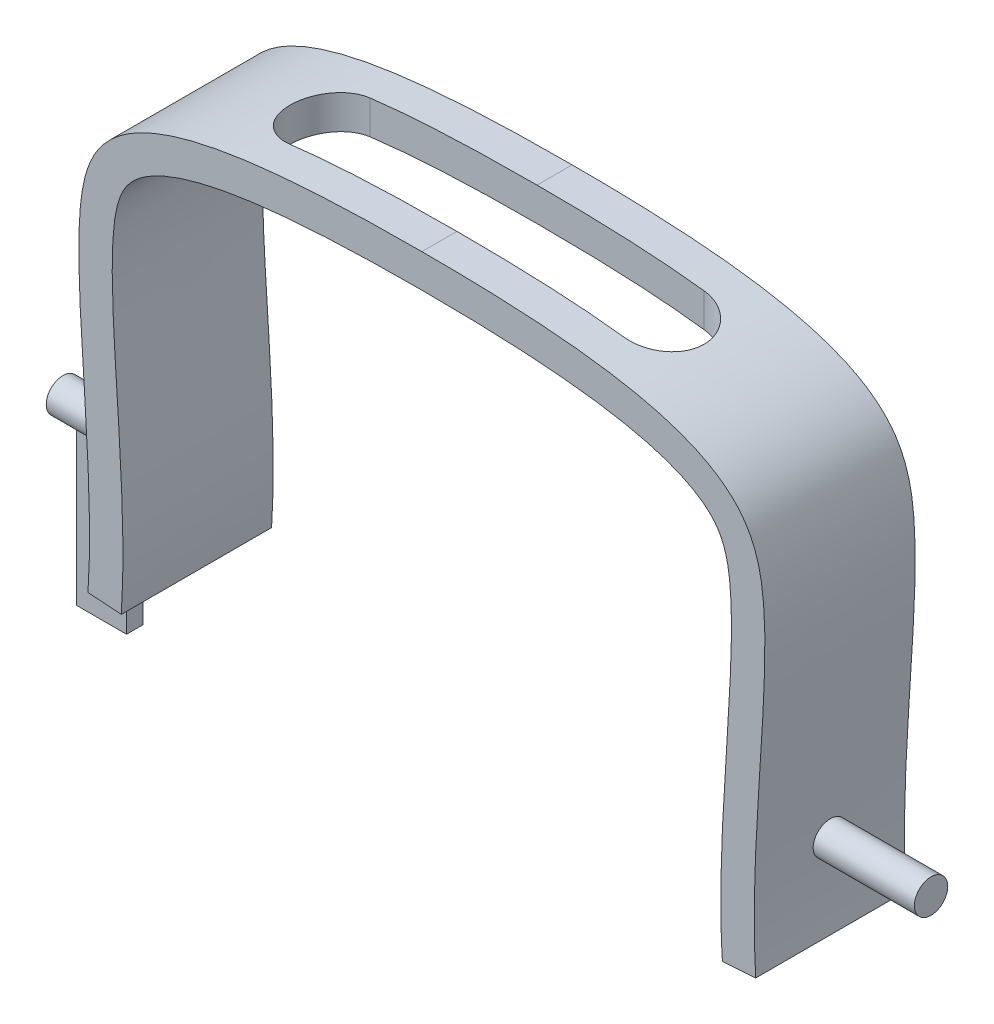
SolidWorks part; units mm, degrees
ref_plane "Front Plane" through (0, 0, 0) normal (0, 0, 1) x (1, 0, 0)
ref_plane "Top Plane" through (0, 0, 0) normal (0, 1, 0) x (1, 0, 0)
ref_plane "Right Plane" through (0, 0, 0) normal (1, 0, 0) x (0, 0, -1)
sketch "Sketch3" plane through (0, 0, 0) normal (0, 0, 1) x (1, 0, 0)
  line L0 (-25.3926, 0.4128) -> (-22.8588, 0.2357)
  line L1 (0, 0) -> (0, 49.1985) construction
  line L2 (22.8588, 0.2357) -> (25.3926, 0.4128)
  spline S0 degree 3 poles (-22.8588, 0.2357) (-22.2073, 9.561) (-24.8571, 24.7477) (-20.4286, 32.2593) (-9.2595, 33.02) (0, 33.02) knots 0 0 0 0 0.433889 0.533889 1 1 1 1
  spline S1 degree 1 poles (-25.3926, 0.4128) (0, 35.56) knots 0 0 1 1 construction
  spline S2 degree 3 poles (22.8588, 0.2357) (22.2073, 9.561) (24.8571, 24.7477) (20.4286, 32.2593) (9.2595, 33.02) (0, 33.02) knots 0 0 0 0 0.433889 0.533889 1 1 1 1
  spline S3 degree 1 poles (25.3926, 0.4128) (0, 35.56) knots 0 0 1 1 construction
  spline S4 degree 3 poles (-25.3926, 0.4128) (-25.3472, 1.0633) (-25.2873, 2.3429) (-25.2559, 5.0926) (-25.3636, 8.6726) (-25.623, 13.0382) (-25.906, 17.2716) (-26.1042, 21.2032) (-26.0979, 24.6856) (-25.8161, 27.1655) (-25.2212, 28.9768) (-24.5105, 30.2231) (-23.5816, 31.2478) (-22.1911, 32.3246) (-20.1914, 33.3182) (-17.4516, 34.1574) (-13.3644, 34.9503) (-8.7163, 35.3649) (-3.7754, 35.5373) (-1.2543, 35.56) (0, 35.56) knots 0 0 0 0 0.03125 0.0625 0.125 0.1875 0.25 0.3125 0.375 0.4375 0.46875 0.5 0.53125 0.5625 0.625 0.6875 0.75 0.875 0.9375 1 1 1 1
  spline S5 degree 3 poles (0, 35.56) (1.2543, 35.56) (3.7754, 35.5373) (8.7163, 35.3649) (13.3644, 34.9503) (17.4516, 34.1574) (20.1914, 33.3182) (22.1911, 32.3246) (23.5816, 31.2478) (24.5105, 30.2231) (25.2212, 28.9768) (25.8161, 27.1655) (26.0979, 24.6856) (26.1042, 21.2032) (25.906, 17.2716) (25.623, 13.0382) (25.3636, 8.6726) (25.2559, 5.0926) (25.2873, 2.3429) (25.3472, 1.0633) (25.3926, 0.4128) knots 0 0 0 0 0.0625 0.125 0.25 0.3125 0.375 0.4375 0.46875 0.5 0.53125 0.5625 0.625 0.6875 0.75 0.8125 0.875 0.9375 0.96875 1 1 1 1
  dimension "D1" = 22.86
  dimension "D2" = 33.02
  dimension "D3" = 2.54
extrude "main body" add sketch "Sketch3" along normal mid plane 11.43
ref_plane "top of rounded bit" through (0, 35.56, 0) normal (0, 1, 0) x (1, 0, 0)
sketch "Sketch4" plane through (0, 35.56, 0) normal (0, 1, 0) x (1, 0, 0)
  line L0 (-12.7, 0) -> (12.7, 0) construction
  line L1 (0, -5.715) -> (0, 5.715) construction
  line L2 (-12.7, 3.048) -> (12.7, 3.048)
  line L3 (-12.7, -3.048) -> (12.7, -3.048)
  arc A0 (-12.7, 3.048) -> (-12.7, -3.048) centre (-12.7, 0) ccw
  arc A1 (12.7, -3.048) -> (12.7, 3.048) centre (12.7, 0) ccw
  point P4 (0, 0)
extrude "slot for joystick" cut sketch "Sketch4" against normal blind 127 and the other way blind 127
ref_plane "nibble plane one" through (-25.3926, 0, 0) normal (1, 0, 0) x (0, 0, -1)
ref_plane "nibble plane two" through (25.3926, 0, 0) normal (1, 0, 0) x (0, 0, -1)
sketch "Sketch5" plane through (25.3926, 0, 0) normal (1, 0, 0) x (0, 0, -1)
  line L0 (-5.715, 0.4128) -> (5.715, 0.4128) construction
  circle A0 centre (0, 6.7628) radius 1.27
  point P2 (0, 0.4128)
  dimension "D1" = 6.35
extrude "nibble two" add sketch "Sketch5" along normal blind 7.62 and the other way up to body
sketch "Sketch6" plane through (-25.3926, 0, 0) normal (1, 0, 0) x (0, 0, -1)
  line L0 (-5.715, 0.4128) -> (5.715, 0.4128) construction
  circle A0 centre (0, 6.7628) radius 1.27
  point P2 (0, 0.4128)
  dimension "D1" = 6.35
extrude "nibble one" add sketch "Sketch6" against normal blind 7.62 and the other way up to body
ref_point "nibble center"
ref_plane "nibble flag plane" through (0, 6.7628, 0) normal (0, 1, 0) x (1, 0, 0)
sketch "Sketch7" plane through (0, 6.7628, 0) normal (0, 1, 0) x (1, 0, 0)
  line L1 (-31.3343, 0.6195) -> (-27.5243, 0.6195)
  line L2 (-31.3343, 0.6195) -> (-31.3343, -0.6505)
  line L3 (-31.3343, -0.6505) -> (-27.5243, -0.6505)
  line L4 (-27.5243, 0.6195) -> (-27.5243, -0.6505)
  line L5 (-31.3343, 0.6195) -> (-27.5243, -0.6505) construction
  line L6 (-31.3343, -0.6505) -> (-27.5243, 0.6195) construction
  point P0 (-29.4293, -0.0155)
  dimension "D1" = 1.27
  dimension "D2" = 3.81
extrude "flag" add sketch "Sketch7" against normal blind 12.7
